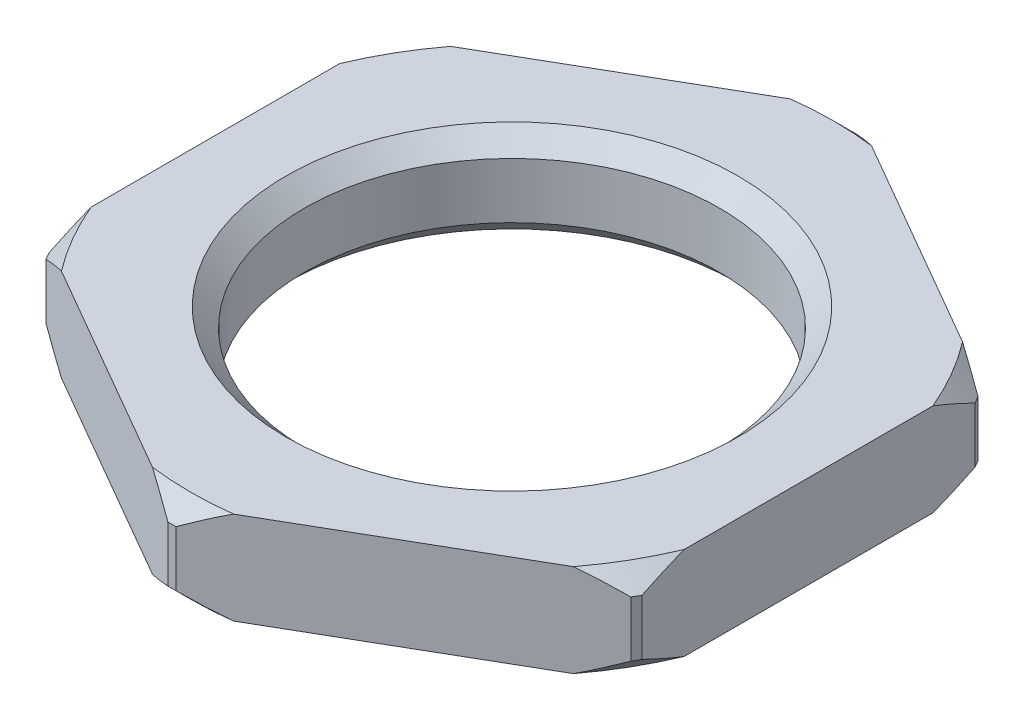
SolidWorks part; units mm, degrees
ref_plane "Front Plane" through (0, 0, 0) normal (0, 0, 1) x (1, 0, 0)
ref_plane "Top Plane" through (0, 0, 0) normal (0, 1, 0) x (1, 0, 0)
ref_plane "Right Plane" through (0, 0, 0) normal (1, 0, 0) x (0, 0, -1)
sketch "Sketch1" plane through (0, 0, 0) normal (0, 1, 0) x (1, 0, 0)
  circle A0 centre (0, 0) radius 9.175
  circle A1 centre (0, 0) radius 5.6
  dimension "D1" = 18.35
  dimension "D2" = 11.2
extrude "Boss-Extrude1" add sketch "Sketch1" along normal mid plane 2.5
chamfer "Chamfer1" distance 0.5 angle 45 2 edges at (0, -1.25, 9.175) (0, 1.25, 9.175)
sketch "Sketch2" plane through (0, 1.25, 0) normal (0, 1, 0) x (1, 0, 0)
  line L1 (0, -9.2376) -> (8, -4.6188)
  line L2 (8, -4.6188) -> (8, 4.6188)
  line L3 (8, 4.6188) -> (0, 9.2376)
  line L4 (0, 9.2376) -> (-8, 4.6188)
  line L5 (-8, 4.6188) -> (-8, -4.6188)
  line L6 (-8, -4.6188) -> (0, -9.2376)
  circle A0 centre (0, 0) radius 8 construction
  circle A1 centre (0, 0) radius 9.175 construction
  circle A2 centre (0, 0) radius 9.175
  circle M7 centre (0, 0) radius 8.675
  dimension "D1" = 16
extrude "Cut-Extrude1" cut sketch "Sketch2" against normal up to next contours L5 M7 | L5 A2 M7 | L4 A2 M7 | L4 M7 | L3 A2 M7 | L3 M7 | L2 A2 M7 | L2 M7 | L1 A2 M7 | L1 M7 | L6 M7 | L6 A2 M7 region at (0.647, 1.25, 8.9678) region at (-4.5426, 1.25, 7.868) region at (4.1355, 1.25, 7.1628) region at (-4.1355, 1.25, 7.1628) region at (8.0906, 1.25, 3.9236) region at (-9.0844, 1.25, 0) region at (8.2709, 1.25, 0) region at (-8.2709, 1.25, 0) region at (-4.5426, 1.25, -7.868) region at (4.3824, 1.25, -7.5906) region at (4.1355, 1.25, -7.1628) region at (-4.1355, 1.25, -7.1628)
chamfer "Chamfer2" distance 0.5 angle 45 2 edges at (0, -1.25, 5.6) (0, 1.25, 5.6)
ref_axis "Center axis" through (0, 11.3759, 0) along (0, -1, 0)
